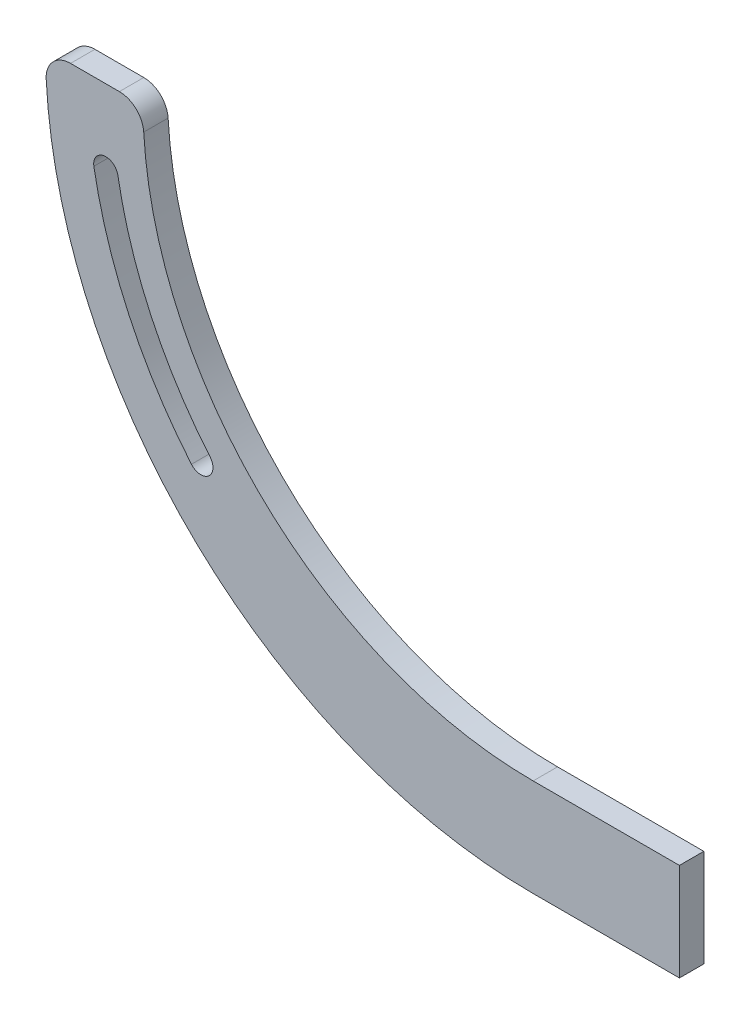
SolidWorks part; units mm, degrees
ref_plane "Front Plane" through (0, 0, 0) normal (0, 0, 1) x (1, 0, 0)
ref_plane "Top Plane" through (0, 0, 0) normal (0, 1, 0) x (1, 0, 0)
ref_plane "Right Plane" through (0, 0, 0) normal (1, 0, 0) x (0, 0, -1)
sketch "Sketch1" plane through (0, 0, 0) normal (0, 0, 1) x (1, 0, 0)
  line L0 (0, 0) -> (-203.2, 0) construction
  line L1 (0, 0) -> (0, -203.2) construction
  line L2 (0, -203.2) -> (76.2, -203.2)
  line L3 (0, -254) -> (76.2, -254)
  line L4 (-254, 0) -> (-203.2, 0)
  line L5 (76.2, -203.2) -> (76.2, -254)
  arc A0 (-203.2, 0) -> (0, -203.2) centre (0, 0) ccw
  arc A1 (-254, 0) -> (0, -254) centre (0, 0) ccw
  dimension "D1" = 50.8
  dimension "D2" = 76.2
  dimension "D3" = 203.2
extrude "Boss-Extrude1" add sketch "Sketch1" along normal blind 12.7
ref_plane "Mid_Plane" through (0, 0, 6.35) normal (0, 0, 1) x (1, 0, 0)
sketch "Sketch2" plane through (0, 0, 12.7) normal (0, 0, 1) x (1, 0, 0)
  line L0 (0, 0) -> (-229.3095, 0) construction
  line L1 (0, 0) -> (-222.5647, -39.2442) construction
  line L2 (0, 0) -> (-173.1246, -145.2688) construction
  arc A0 (-222.5647, -39.2442) -> (-173.1246, -145.2688) centre (0, 0) ccw construction
  arc A1 (-222.5647, -39.2442) -> (-173.1246, -145.2688) centre (0, 0) ccw construction
  arc A2 (-228.8182, -40.3468) -> (-177.989, -149.3505) centre (0, 0) ccw
  arc A3 (-216.3112, -38.1415) -> (-168.2602, -141.1871) centre (0, 0) ccw
  arc A4 (-216.3112, -38.1415) -> (-228.8182, -40.3468) centre (-222.5647, -39.2442) ccw
  arc A5 (-177.989, -149.3505) -> (-168.2602, -141.1871) centre (-173.1246, -145.2688) ccw
  point P5 (-204.8238, -95.5109)
  dimension "D1" = 30
  dimension "D3" = 12.7
  dimension "D2" = 10
extrude "Cut-Extrude1" cut sketch "Sketch2" against normal up to next
fillet "Fillet1" radius 12.7 2 edges at (-203.2, 0, 6.35) (-254, 0, 6.35)
ref_point "Mid_Point"
